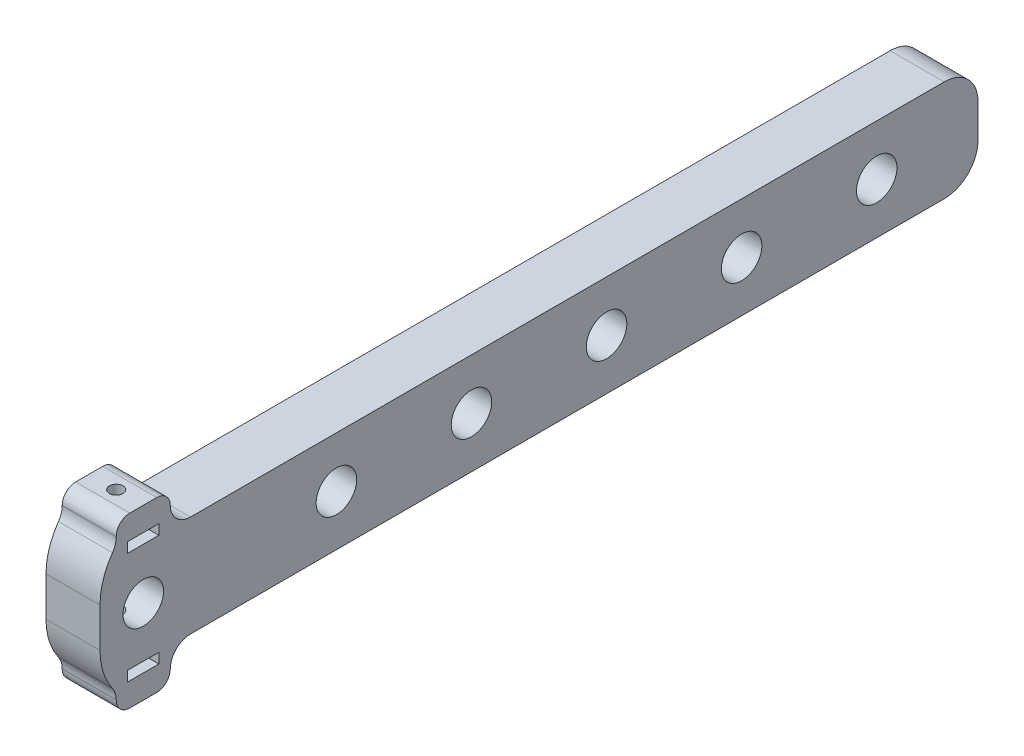
SolidWorks part; units mm, degrees
ref_plane "前视基准面" through (0, 0, 0) normal (0, 0, 1) x (1, 0, 0)
ref_plane "上视基准面" through (0, 0, 0) normal (0, 1, 0) x (1, 0, 0)
ref_plane "右视基准面" through (0, 0, 0) normal (1, 0, 0) x (0, 0, -1)
other "Configuration Table"
sketch "草图1" plane through (0, 0, 0) normal (1, 0, 0) x (0, 0, -1)
  line L1 (0, 0) -> (130, 0)
  line L2 (0, 0) -> (0, 15)
  line L3 (0, 15) -> (130, 15)
  line L4 (130, 0) -> (130, 15)
  dimension "D1" = 15
  dimension "D2" = 130
extrude "凸台-拉伸1" add sketch "草图1" along normal blind 8
sketch "草图15" plane through (0, 0, 0) normal (-1, 0, 0) x (0, 0, 1)
  line L0 (0, 15) -> (0, 0) construction
  circle A2 centre (-6.4, 7.5) radius 3
  dimension "D1" = 6
  dimension "D2" = 6.4
sketch "草图17" plane through (0, 0, 0) normal (-1, 0, 0) x (0, 0, 1)
  line L0 (-130, 7.5) -> (-31.7081, 7.5) construction
  line L1 (-130, 0) -> (-130, 15) construction
  circle A0 centre (-115, 7.5) radius 3
  circle A1 centre (-95, 7.5) radius 3
  circle A2 centre (-75, 7.5) radius 3
  circle A3 centre (-55, 7.5) radius 3
  circle A4 centre (-35, 7.5) radius 3
  dimension "D6" = 6
  dimension "D7" = 6
  dimension "D8" = 6
  dimension "D9" = 6
  dimension "D10" = 6
  dimension "D1" = 15
  dimension "D2" = 20
  dimension "D3" = 20
  dimension "D4" = 20
  dimension "D5" = 20
extrude "切除-拉伸10" cut sketch "草图17" against normal up to next
ref_plane "基准面1" through (0, 0, -6.4) normal (0, 0, 1) x (1, 0, 0)
extrude "切除-拉伸12" cut sketch "草图15" against normal up to next
sketch "草图22" plane through (0, 15, 0) normal (0, 1, 0) x (1, 0, 0)
  line L0 (0, 130) -> (0, 0) construction
  line L1 (0, 10.4) -> (8, 10.4)
  line L2 (0, 10.4) -> (0, 2.4)
  line L3 (0, 2.4) -> (8, 2.4)
  line L4 (8, 10.4) -> (8, 2.4)
  line L5 (8, 130) -> (8, 0) construction
  line L6 (0, 6.4) -> (8, 6.4) construction
  line L8 (8, 130) -> (0, 130) construction
  dimension "D1" = 8
  dimension "D2" = 123.6
  dimension "D3" = 4
extrude "凸台-拉伸7" add sketch "草图22" along normal blind 5
ref_plane "基准面2" through (0, 7.5, 0) normal (0, 1, 0) x (1, 0, 0)
ref_plane "基准面3" through (0, 15, 0) normal (0, 1, 0) x (1, 0, 0)
sketch "草图24" plane through (0, 15, 0) normal (0, 1, 0) x (1, 0, 0)
  line L1 (4, 4.0906) -> (6, 5.2453)
  line L2 (6, 5.2453) -> (6, 7.5547)
  line L3 (6, 7.5547) -> (4, 8.7094)
  line L4 (4, 8.7094) -> (2, 7.5547)
  line L5 (2, 7.5547) -> (2, 5.2453)
  line L6 (2, 5.2453) -> (4, 4.0906)
  circle A0 centre (4, 6.4) radius 2 construction
  dimension "D1" = 4
extrude "切除-拉伸18" cut sketch "草图24" along normal blind 1.5
sketch "草图25" plane through (8, 0, 0) normal (1, 0, 0) x (0, 0, -1)
  line L0 (6.4, 20) -> (6.4, 15) construction
  line L1 (2.4, 20) -> (10.4, 20) construction
  line L2 (2.2, 15) -> (-2.2, 15) construction
  line L4 (4.09, 15) -> (8.71, 15)
  line L5 (4.09, 15) -> (4.09, 16.5)
  line L6 (4.09, 16.5) -> (8.71, 16.5)
  line L7 (8.71, 15) -> (8.71, 16.5)
  dimension "D1" = 1.5
  dimension "D2" = 4.62
  dimension "D3" = 2.31
extrude "切除-拉伸19" cut sketch "草图25" against normal blind 4 contours L5 L6 L7 L4
fillet "圆角8" radius 3 2 edges at (4, 15, -10.4) (4, 15, -2.4)
fillet "圆角9" radius 2 2 edges at (4, 20, -2.4) (4, 20, -10.4)
mirror "镜向6" about plane through (0, 7.5, 0) normal (0, 1, 0) of "切除-拉伸19", "切除-拉伸18", "凸台-拉伸7"
fillet "圆角10" radius 2 2 edges at (4, -5, -2.4) (4, -5, -10.4)
fillet "圆角11" radius 3 2 edges at (4, 0, -2.4) (4, 0, -10.4)
sketch "草图21" plane through (0, 15, 0) normal (0, 1, 0) x (1, 0, 0)
  line L0 (0, 6.4) -> (8, 6.4) construction
  line L1 (8, 130) -> (0, 130) construction
  line L4 (0, 130) -> (0, 13.4) construction
  line L5 (8, 130) -> (8, 13.4) construction
  circle A0 centre (4, 6.4) radius 1
  dimension "D2" = 2
  dimension "D1" = 123.6
extrude "切除-拉伸20" cut sketch "草图21" against normal blind 28.5 and the other way blind 15.5
fillet "圆角12" radius 10 2 edges at (4, 0, 0) (4, 15, 0)
fillet "圆角13" radius 5 2 edges at (4, 15, -130) (4, 0, -130)
